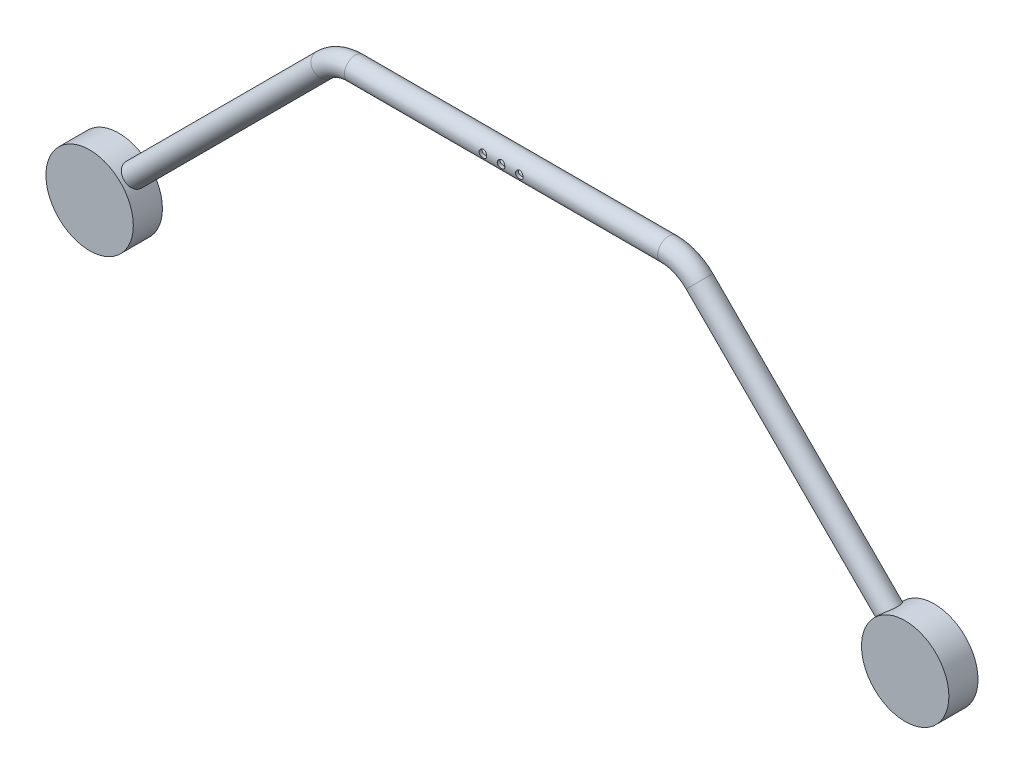
SolidWorks part; units mm, degrees
ref_plane "Front Plane" through (0, 0, 0) normal (0, 0, 1) x (1, 0, 0)
ref_plane "Top Plane" through (0, 0, 0) normal (0, 1, 0) x (1, 0, 0)
ref_plane "Right Plane" through (0, 0, 0) normal (1, 0, 0) x (0, 0, -1)
sketch "Sketch1" plane through (0, 0, 0) normal (0, 0, 1) x (1, 0, 0)
  line L10 (0, 19.4566) -> (0, -8.1997) construction
  line L11 (-355.6, -203.2) -> (-355.6, -165.1) construction
  line L12 (355.6, -203.2) -> (355.6, -165.1) construction
  circle A0 centre (-355.6, -203.2) radius 38.1
  circle A3 centre (-355.6, -203.2) radius 85.471 construction
  circle A4 centre (355.6, -203.2) radius 38.1
  circle A5 centre (355.6, -203.2) radius 85.471 construction
  point P16 (-355.6, -185.2)
  point P17 (355.6, -185.2)
  dimension "D5" = 76.2
  dimension "D6" = 170.942
  dimension "D4" = 18
  dimension "D7" = 18
  dimension "D8" = 711.2
  dimension "D1" = 203.2
extrude "Boss-Extrude1" add sketch "Sketch1" along normal blind 25.4 contours A0 | A4 | A0 | A4 region at (-355.6, -203.2, 0) region at (355.6, -203.2, 0)
ref_plane "Plane1" through (0, 0, 12.7) normal (0, 0, 1) x (1, 0, 0)
sketch "Sketch4" plane through (0, 0, 12.7) normal (0, 0, 1) x (1, 0, 0)
  line L0 (-355.6, -203.2) -> (-163.5592, -11.1592)
  line L1 (-136.6185, 0) -> (136.6185, 0)
  line L2 (163.5592, -11.1592) -> (355.6, -203.2)
  arc A0 (136.6185, 0) -> (163.5592, -11.1592) centre (136.6185, -38.1) cw
  arc A1 (-163.5592, -11.1592) -> (-136.6185, 0) centre (-136.6185, -38.1) cw
  dimension "D1" = 38.1
  dimension "D2" = 711.2
  dimension "D3" = 203.2
  dimension "D4" = 135
sweep "Sweep1" add path "Sketch4" circular profile diameter 19.05 parameters "D3"=19.05
sketch "Sketch23" plane through (0, 0, 25.4) normal (0, 0, 1) x (1, 0, 0)
  line L0 (-15.875, 0) -> (15.875, 0) construction
  dimension "D1" = 31.75
shell "Shell1" thickness 2.54 removed face at (348.8648, -209.9352, 12.7) removed face at (-348.8648, -209.9352, 12.7)
hole_wizard "M6 Clearance Hole1" positions "3DSketch1" profile "Sketch49" hole size "M6" standard "ANSI Metric" end condition through all
sketch3d "3DSketch1"
  point P0 (-15.875, 0, 22.225)
  point P2 (15.875, 0, 22.225)
sketch "Sketch49" plane through (-15.875, 0, 22.225) normal (1, 0, 0) x (0, -1, 0)
  line L0 (0, 0) -> (0, 22.225)
  line L1 (0, 22.225) -> (3.3, 22.225)
  line L2 (3.3, 22.225) -> (3.3, 0.025)
  line L3 (3.3, 0.025) -> (3.325, 0)
  line L5 (3.325, 0) -> (0, 0)
  line L6 (-3.3, 0.025) -> (-3.325, 0) construction
  line L11 (0, -6.35) -> (0, 107.95) construction
  dimension "Thru Hole Dia." = 6.6
  dimension "Thru Hole Depth" = 22.225
  dimension "Near C'Sink Dia." = 6.65
  dimension "Near C'Sink Angle" = 90
hole_wizard "M6 Clearance Hole2" positions "3DSketch2" profile "Sketch51" hole size "M6" standard "ANSI Metric" end condition through all
sketch3d "3DSketch2"
  point P0 (0, 0, 22.225)
sketch "Sketch51" plane through (0, 0, 22.225) normal (1, 0, 0) x (0, -1, 0)
  line L0 (0, 0) -> (0, 22.225)
  line L1 (0, 22.225) -> (3.3, 22.225)
  line L2 (3.3, 22.225) -> (3.3, 0.025)
  line L3 (3.3, 0.025) -> (3.325, 0)
  line L5 (3.325, 0) -> (0, 0)
  line L6 (-3.3, 0.025) -> (-3.325, 0) construction
  line L11 (0, -6.35) -> (0, 107.95) construction
  dimension "Thru Hole Dia." = 6.6
  dimension "Thru Hole Depth" = 22.225
  dimension "Near C'Sink Dia." = 6.65
  dimension "Near C'Sink Angle" = 90
equation "\"Rover_Length\"= 25in"
equation "\"Rover_Width\"= 18in"
equation "\"Rover_Height\"= 12in"
equation "\"Chassis_Wheelbase\"= 28in"
equation "\"Chassis_WheelDiam\"= 171mm"
equation "\"Chassis_ArmDiamWidth\"= 0.75in"
equation "\"Chassis_ArmAngle\"= 135deg"
equation "\"Chassis_HubMountOD\"= 3in"
equation "\"Chassis_WheelBoltHole\"= 36mm"
equation "\"Chassis_WheelBoltNum\"= 4"
equation "\"Chassis_DiffBarLength\"= 12in"
equation "\"Chassis_DiffBarWidth\"= 1in"
equation "\"Chassis_DiffBarHeight\"= 0.5in"
equation "\"Chassis_DiffLinkage_Length\"= 2.5in"
equation "\"D5@Sketch1\"=\"Chassis_HubMountOD\""
equation "\"D4@Sketch1\"=\"Chassis_WheelBoltHole\"/2"
equation "\"D7@Sketch1\"=\"Chassis_WheelBoltHole\"/2"
equation "\"D8@Sketch1\"=\"Chassis_Wheelbase\""
equation "\"D1@Boss-Extrude1\"=\"Chassis_DiffBarWidth\""
equation "\"D2@Sketch4\"=\"Chassis_Wheelbase\""
equation "\"Chassis_ArmHeight\"= 8in"
equation "\"Chassis_MountBracketThickness\"= 0.125in"
equation "\"Chassis_MountBracketWidth\"= 3in"
equation "\"Chassis_MountBacketOverlap\"= 0.5in"
equation "\"Chassis_ArmShaftDiam\"= 0.75in"
equation "\"D3@Sketch4\"=\"Chassis_ArmHeight\""
equation "\"D4@Sketch4\"=\"Chassis_ArmAngle\""
equation "\"D1@Sketch1\"=\"Chassis_ArmHeight\""
equation "\"Chassis_ArmHoleSpacing\" = 1.25in"
equation "\"D1@Sketch23\"=\"Chassis_ArmHoleSpacing\""
